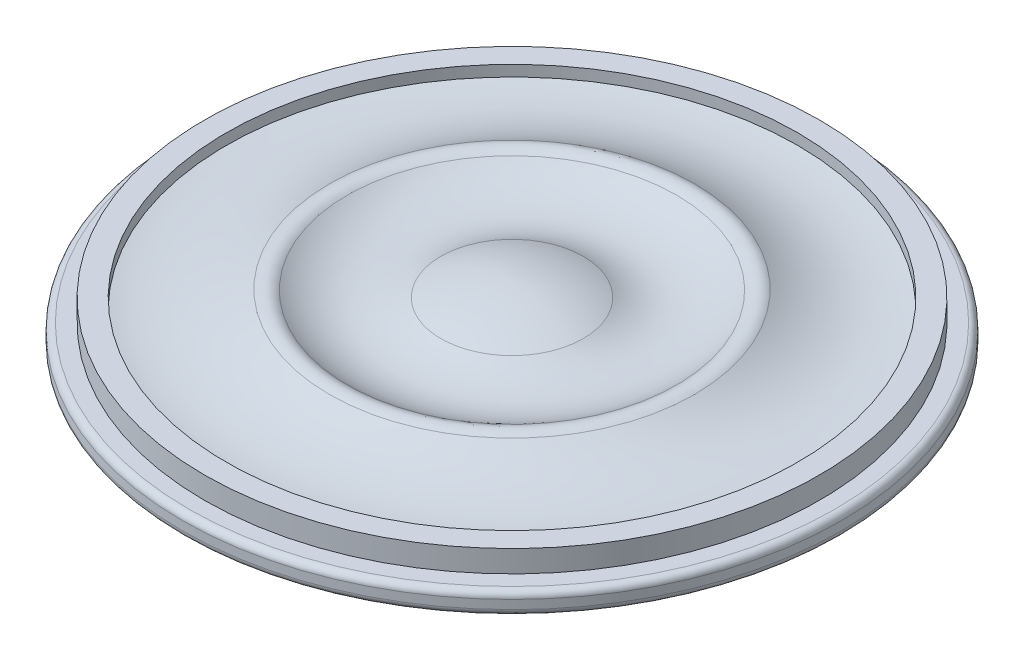
SolidWorks part; units mm, degrees
ref_plane "Plan de face" through (0, 0, 0) normal (0, 0, 1) x (1, 0, 0)
ref_plane "Plan de dessus" through (0, 0, 0) normal (0, 1, 0) x (1, 0, 0)
ref_plane "Plan de droite" through (0, 0, 0) normal (1, 0, 0) x (0, 0, -1)
sketch "Esquisse1" plane through (0, 0, 0) normal (0, 0, 1) x (1, 0, 0)
  line L0 (0, 0) -> (8, 0)
  line L1 (8, 0) -> (8, 1.5)
  line L2 (8, 1.5) -> (13, 1.5)
  line L3 (13, 1.5) -> (13, 2)
  line L4 (13, 2) -> (15, 2)
  line L5 (15, 2) -> (15, 3)
  line L6 (15, 3) -> (14, 3)
  line L7 (14, 3) -> (14, 4)
  line L8 (14, 4) -> (13, 4)
  line L9 (13, 4) -> (13, 3.5)
  line L10 (0, 0) -> (0, 22.8471) construction
  line L11 (0, 0) -> (0, 4.7)
  arc A0 (13, 3.5) -> (8.3102, 4.3293) centre (11.7756, 10.2513) cw
  arc A1 (0, 4.7) -> (3.2429, 4) centre (-0.2612, -4.3717) cw
  arc A2 (3.2429, 4) -> (7.4913, 4.2914) centre (5.1312, 7.5842) ccw
  arc A3 (8.3102, 4.3293) -> (7.4913, 4.2914) centre (7.9299, 3.6794) ccw
  dimension "D10" = 1
  dimension "D1" = 15
  dimension "D2" = 8
  dimension "D3" = 5
  dimension "D4" = 1.5
  dimension "D5" = 0.5
  dimension "D6" = 1
  dimension "D7" = 1
  dimension "D8" = 1
  dimension "D9" = 0.5
  dimension "D12" = 4.7
  dimension "D13" = 4
revolve "Révolution1" add sketch "Esquisse1" angle 360 about L10
sketch "Esquisse2" plane through (0, 1.5, 0) normal (0, -1, 0) x (1, 0, 0)
  circle A0 centre (-4.9267, 9.4846) radius 1.267
extrude "Enlèv. mat.-Extru.1" cut sketch "Esquisse2" against normal blind 1
ref_axis "Axe1" through (0, -0.235, 0) along (0, 1, 0)
pattern_circular "Répétition circulaire1" count 12 over 360 about axis through (0, -0.235, 0) along (0, 1, 0) of "Enlèv. mat.-Extru.1"
fillet "Congé1" radius 0.3 4 edges at (0, 3, -15) (0, 2, -15) (0, 1.5, -13) (0, 0, -8)
